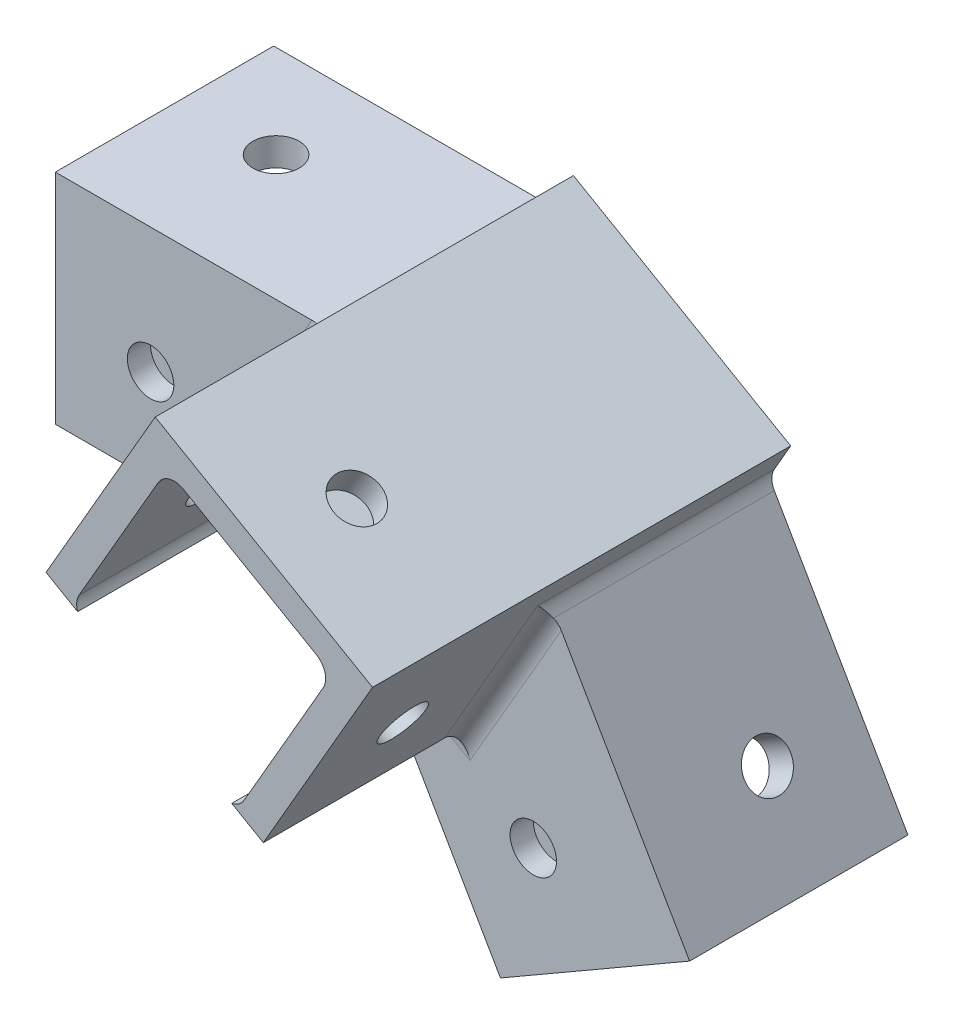
SolidWorks part; units mm, degrees
material "ABS"
ref_plane "Front Plane" through (0, 0, 0) normal (0, 0, 1) x (1, 0, 0)
ref_plane "Top Plane" through (0, 0, 0) normal (0, 1, 0) x (1, 0, 0)
ref_plane "Right Plane" through (0, 0, 0) normal (1, 0, 0) x (0, 0, -1)
ref_plane "Plane1" through (0, 0, 23.5) normal (0, 0, 1) x (1, 0, 0)
sketch "Sketch1" plane through (0, 0, 23.5) normal (0, 0, 1) x (1, 0, 0)
  line L0 (0, 0) -> (0, 23.5)
  line L1 (0, 23.5) -> (25, 23.5)
  line L2 (25, 23.5) -> (37.5, 1.8494)
  line L3 (37.5, 1.8494) -> (17.1484, -9.9006)
  line L4 (17.1484, -9.9006) -> (11.4323, 0)
  line L5 (11.4323, 0) -> (0, 0)
  dimension "D1" = 23.5
  dimension "D2" = 120
  dimension "D3" = 25
extrude "Boss-Extrude1" add sketch "Sketch1" against normal blind 23.5
sketch "Sketch2" plane through (0, 0, 23.5) normal (0, 0, -1) x (-1, 0, 0)
  line L0 (-17.1484, -9.9006) -> (-34.9019, 0.3494)
  line L1 (0, 20.5) -> (20.5, 20.5)
  line L2 (0, 20.5) -> (0, 0)
  line L3 (0, 0) -> (20.5, 0)
  line L4 (20.5, 20.5) -> (20.5, 0)
  line L5 (-17.1484, -9.9006) -> (-27.3984, -27.6542)
  line L6 (-34.9019, 0.3494) -> (-45.1519, -17.4042)
  line L7 (-27.3984, -27.6542) -> (-45.1519, -17.4042)
  line L8 (-17.1484, -9.9006) -> (-37.5, 1.8494) construction
  dimension "D1" = 20.5
  dimension "D2" = 20.5
extrude "Boss-Extrude2" add sketch "Sketch2" along normal blind 3 separate body
sketch "Sketch5" plane through (0, 0, 0) normal (0, 0, -1) x (-1, 0, 0)
  line L0 (20.5, 20.5) -> (20.5, 0) construction
  line L1 (0, 20.5) -> (20.5, 20.5)
  line L2 (0, 20.5) -> (0, 23.5)
  line L3 (0, 23.5) -> (20.5, 23.5)
  line L4 (20.5, 20.5) -> (20.5, 23.5)
  line L5 (-25, 23.5) -> (0, 23.5) construction
  line L6 (-34.9019, 0.3494) -> (-37.5, 1.8494)
  line L7 (-34.9019, 0.3494) -> (-45.1519, -17.4042)
  line L8 (-37.5, 1.8494) -> (-47.75, -15.9042)
  line L9 (-45.1519, -17.4042) -> (-47.75, -15.9042)
  line L10 (-27.3984, -27.6542) -> (-45.1519, -17.4042) construction
extrude "Boss-Extrude4" add sketch "Sketch5" against normal blind 23.5
sketch "Sketch6" plane through (0, 0, 20.5) normal (0, 0, 1) x (1, 0, 0)
  line L0 (-20.5, 20.5) -> (-20.5, 0) construction
  line L1 (-20.5, 10.25) -> (0, 10.25) construction
  line L2 (0, 0) -> (0, 20.5) construction
  line L3 (26.0252, -4.7756) -> (6.645, 28.7918) construction
  line L4 (34.9019, 0.3494) -> (17.1484, -9.9006) construction
  line L5 (36.2752, -22.5292) -> (26.0252, -4.7756) construction
  line L6 (27.3984, -27.6542) -> (45.1519, -17.4042) construction
  line L7 (-0.25, 13) -> (-20.25, 13)
  line L8 (-0.25, 13) -> (-0.25, 7.5)
  line L9 (-20.25, 13) -> (-20.25, 7.5)
  line L10 (-0.25, 7.5) -> (-20.25, 7.5)
  line L11 (-0.25, 13) -> (-20.25, 7.5) construction
  line L12 (-20.25, 13) -> (-0.25, 7.5) construction
  line L13 (23.7686, -6.3671) -> (33.7686, -23.6876)
  line L14 (23.7686, -6.3671) -> (28.5317, -3.6171)
  line L15 (33.7686, -23.6876) -> (38.5317, -20.9376)
  line L16 (28.5317, -3.6171) -> (38.5317, -20.9376)
  line L17 (23.7686, -6.3671) -> (38.5317, -20.9376) construction
  line L18 (33.7686, -23.6876) -> (28.5317, -3.6171) construction
  line L19 (17.1484, -9.9006) -> (34.9019, 0.3494) construction
  point P14 (-10.25, 10.25)
  point P15 (31.1502, -13.6524)
  dimension "D1" = 20
  dimension "D2" = 5.5
sketch "Sketch8" plane through (0, 20.5, 0) normal (0, -1, 0) x (1, 0, 0)
  line L0 (-20.5, 10.25) -> (0, 10.25) construction
  line L1 (-20.5, 20.5) -> (-20.5, 0) construction
  line L2 (0, 0) -> (0, 20.5) construction
  line L3 (-20.5, 0) -> (0, 0) construction
  line L4 (-0.25, 7.5) -> (-20.25, 7.5)
  line L5 (-0.25, 7.5) -> (-0.25, 13)
  line L6 (-20.25, 7.5) -> (-20.25, 13)
  line L7 (-0.25, 13) -> (-20.25, 13)
  line L8 (-0.25, 7.5) -> (-20.25, 13) construction
  line L9 (-20.25, 7.5) -> (-0.25, 13) construction
  point P9 (-10.25, 10.25)
  dimension "D1" = 10.25
  dimension "D2" = 5.5
  dimension "D3" = 20
sketch "Sketch10" plane through (26.3277, 15.2003, 0) normal (-0.866, -0.5, 0) x (0, 0, 1)
  line L0 (10.25, -37.6484) -> (10.25, -17.1484) construction
  line L1 (20.5, -37.6484) -> (0, -37.6484) construction
  line L2 (0, -17.1484) -> (20.5, -17.1484) construction
  line L3 (7.5, -17.3984) -> (7.5, -37.3984)
  line L4 (7.5, -17.3984) -> (13, -17.3984)
  line L5 (7.5, -37.3984) -> (13, -37.3984)
  line L6 (13, -17.3984) -> (13, -37.3984)
  line L7 (7.5, -17.3984) -> (13, -37.3984) construction
  line L8 (7.5, -37.3984) -> (13, -17.3984) construction
  point P7 (10.25, -27.3984)
  dimension "D1" = 5.5
  dimension "D2" = 20
sketch "Sketch12" plane through (0, 0, 0) normal (0, 0, -1) x (-1, 0, 0)
  line L1 (-23.3827, -6.3013) -> (0, 7.1987)
  line L2 (-23.3827, -6.3013) -> (-35.1327, 14.0503)
  line L3 (0, 7.1987) -> (-11.75, 27.5503)
  line L4 (-35.1327, 14.0503) -> (-11.75, 27.5503)
  line L5 (-23.3827, -6.3013) -> (-11.75, 27.5503) construction
  line L6 (0, 7.1987) -> (-35.1327, 14.0503) construction
  line L7 (0, 0) -> (0, 20.5) construction
  line L8 (-17.1484, -9.9006) -> (-34.9019, 0.3494) construction
  line L9 (-11.4323, 0) -> (-25, 23.5) construction
  point P5 (-17.5663, 10.6245)
  dimension "D1" = 27
  dimension "D2" = 23.5
extrude "Boss-Extrude9" add sketch "Sketch12" against normal blind 45
sketch "Sketch13" plane through (0, 0, 45) normal (0, 0, 1) x (1, 0, 0)
  line L0 (2.5646, 5.1407) -> (13.0646, 23.3273)
  line L1 (2.5646, 5.1407) -> (20.3181, -5.1093)
  line L2 (13.0646, 23.3273) -> (30.8181, 13.0773)
  line L3 (20.3181, -5.1093) -> (30.8181, 13.0773)
  line L4 (2.5646, 5.1407) -> (30.8181, 13.0773) construction
  line L5 (13.0646, 23.3273) -> (20.3181, -5.1093) construction
  line L7 (11.4323, 0) -> (23.4413, 20.8003) construction
  line L8 (35.1327, 14.0503) -> (11.75, 27.5503) construction
  line L9 (11.75, 27.5503) -> (35.1327, 14.0503) construction
  line L10 (35.1327, 14.0503) -> (11.75, 27.5503) construction
  point P1 (16.6913, 9.109)
  dimension "D1" = 21
  dimension "D2" = 20.5
  dimension "D3" = 3
extrude "Cut-Extrude4" cut sketch "Sketch13" against normal blind 40
fillet "Fillet5" radius 3 1 edges at (11.4323, 0, 11.75)
sketch "Sketch14" plane through (0, 0, 0) normal (0, 0, -1) x (-1, 0, 0)
  line L0 (-18.7654, 23.5) -> (-28.1173, 18.1007)
  line L1 (-18.7654, 23.5) -> (-20.7654, 26.9641)
  line L2 (-28.1173, 18.1007) -> (-30.1173, 21.5648)
  line L3 (-20.7654, 26.9641) -> (-30.1173, 21.5648)
  dimension "D1" = 4
extrude "Cut-Extrude5" cut sketch "Sketch14" against normal through all
fillet "Fillet7" radius 2 6 edges at (40.0269, -8.5274, 20.5) (-10.25, 20.5, 20.5) (13.0646, 23.3273, 25) (30.8181, 13.0773, 25) (20.3181, -5.1093, 14.25) (2.5646, 5.1407, 14.25)
sketch "Sketch16" plane through (0, 20.5, 0) normal (0, -1, 0) x (1, 0, 0)
  line L0 (-10.25, 20.5) -> (-10.25, 0) construction
  line L1 (-20.5, 20.5) -> (0, 20.5) construction
  line L2 (-20.5, 0) -> (0, 0) construction
  circle A0 centre (-10.25, 10) radius 2.5
  dimension "D1" = 5
  dimension "D2" = 10
extrude "Cut-Extrude7" cut sketch "Sketch16" against normal blind 40
sketch "Sketch17" plane through (26.3277, 15.2003, 0) normal (-0.866, -0.5, 0) x (0, 0, 1)
  line L0 (0, -27.3984) -> (20.5, -27.3984) construction
  line L1 (0, -17.1484) -> (0, -37.6484) construction
  line L2 (20.5, -17.1484) -> (20.5, -37.6484) construction
  circle A0 centre (10, -27.3984) radius 2.5
  dimension "D1" = 5
  dimension "D2" = 10
extrude "Cut-Extrude8" cut sketch "Sketch17" against normal through all
sketch "Sketch18" plane through (0, 0, 20.5) normal (0, 0, -1) x (-1, 0, 0)
  line L0 (10.25, 0) -> (10.25, 20.5) construction
  line L1 (20.5, 0) -> (0, 0) construction
  line L2 (20.5, 20.5) -> (0, 20.5) construction
  line L4 (-17.1484, -9.9006) -> (-27.3984, -27.6542) construction
  line L5 (-22.2734, -18.7774) -> (-42.625, -7.0274) construction
  line L6 (-47.75, -15.9042) -> (-32.7942, 10) construction
  circle A0 centre (10.25, 10) radius 2.5
  circle A1 centre (-30.9337, -13.7774) radius 2.5
  dimension "D1" = 5
  dimension "D2" = 5
  dimension "D3" = 10
  dimension "D4" = 10
extrude "Cut-Extrude9" cut sketch "Sketch18" against normal through all from offset 0.5 offset against normal yes
sketch "Sketch19" plane through (20.2655, -11.7003, 0) normal (0.866, -0.5, 0) x (0, 0, -1)
  line L0 (-25, 16.2343) -> (-45, 16.2343) construction
  line L2 (-45, 6.2343) -> (-45, 29.7343) construction
  line L4 (-45, 6.2343) -> (-23.5, 6.2343) construction
  line L5 (-45, 6.2343) -> (-45, 29.7343) construction
  circle A0 centre (-35, 16.2343) radius 2.5
  dimension "D1" = 5
  dimension "D2" = 10
  dimension "D3" = 10
extrude "Cut-Extrude10" cut sketch "Sketch19" against normal through all
sketch "Sketch21" plane through (0, 0, 5) normal (0, 0, 1) x (1, 0, 0)
  line L0 (21.9413, 18.2023) -> (11.4413, 0.0157) construction
  line L3 (14.7966, 22.3273) -> (29.0861, 14.0773) construction
  line L4 (18.5861, -4.1093) -> (4.2966, 4.1407) construction
  circle A0 centre (16.6913, 9.109) radius 2.5
  dimension "D1" = 5
extrude "Cut-Extrude12" cut sketch "Sketch21" against normal through all
sketch "Sketch22" plane through (13.3671, 23.1526, 0) normal (-0.5, -0.866, 0) x (0.866, -0.5, 0)
  line L0 (9.9006, 45) -> (9.9006, 23.5) construction
  line L1 (1.6506, 45) -> (18.1506, 45) construction
  line L2 (11.4006, 23.5) -> (8.4006, 23.5) construction
  circle A0 centre (9.9006, 35) radius 2.5
  dimension "D1" = 5
  dimension "D2" = 10
extrude "Cut-Extrude13" cut sketch "Sketch22" against normal through all
fillet "Fillet8" radius 2 4 edges at (28.0885, 1.8494, 23.5) (32.7942, 10, 11.75) (9.4115, 23.5, 11.75) (4.7058, 15.3494, 23.5)
sketch "Sketch24" plane through (0, 0, 20.5) normal (0, 0, -1) x (-1, 0, 0)
  line L0 (-27.3984, -27.6542) -> (-25.3984, -24.1901)
  line L1 (20.5, 0) -> (16.5, 0)
  line L2 (20.5, 0) -> (20.5, 4)
  line L3 (20.5, 4) -> (16.5, 4)
  line L4 (16.5, 0) -> (16.5, 4)
  line L5 (-27.3984, -27.6542) -> (-30.8625, -25.6542)
  line L6 (-25.3984, -24.1901) -> (-28.8625, -22.1901)
  line L7 (-30.8625, -25.6542) -> (-28.8625, -22.1901)
  line L8 (-17.1484, -9.9006) -> (-27.3984, -27.6542) construction
  line L9 (-27.5814, -26.9711) -> (-26.0814, -24.3731)
  line L10 (-26.0814, -24.3731) -> (-28.6795, -22.8731)
  line L11 (-30.1795, -25.4711) -> (-28.6795, -22.8731)
  line L12 (-27.5814, -26.9711) -> (-30.1795, -25.4711)
  line L13 (20, 0.5) -> (17, 0.5)
  line L14 (17, 0.5) -> (17, 3.5)
  line L15 (20, 3.5) -> (17, 3.5)
  line L16 (20, 0.5) -> (20, 3.5)
  dimension "D2" = 4
  dimension "D3" = 4
  dimension "D1" = 0.5
extrude "Boss-Extrude13" add sketch "Sketch24" along normal up to surface (20.5 mm away) up to face at (14.1913, 9.109, 0)
fillet "Fillet10" radius 2 1 edges at (0.8345, 6.7169, 23.5)
sketch "Sketch25" plane through (0, 0, 0) normal (0, 0, -1) x (-1, 0, 0)
  line L0 (-28.6795, -22.8731) -> (-30.1795, -25.4711)
  line L1 (-28.6795, -22.8731) -> (-26.0814, -24.3731)
  line L2 (-30.1795, -25.4711) -> (-27.5814, -26.9711)
  line L3 (-26.0814, -24.3731) -> (-27.5814, -26.9711)
  line L4 (20, 3.5) -> (20, 0.5)
  line L5 (20, 3.5) -> (17, 3.5)
  line L6 (20, 0.5) -> (17, 0.5)
  line L7 (17, 3.5) -> (17, 0.5)
  line L8 (-27.5814, -26.9711) -> (-26.0814, -24.3731) construction
  line L9 (17, 3.5) -> (17, 0.5) construction
extrude "Boss-Extrude14" add sketch "Sketch25" against normal blind 4
equation "\"D2@Sketch18\"=\"D1@Sketch18\""
